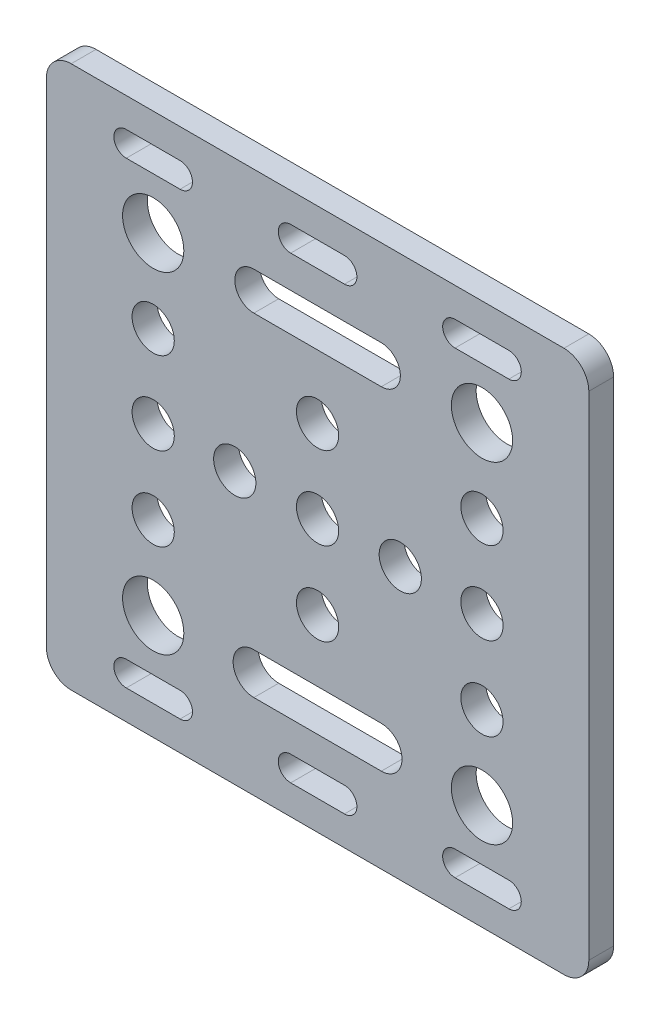
SolidWorks part; units mm, degrees
material "Plastique personnalisé"
ref_plane "Plan de face" through (0, 0, 0) normal (0, 0, 1) x (1, 0, 0)
ref_plane "Plan de dessus" through (0, 0, 0) normal (0, 1, 0) x (1, 0, 0)
ref_plane "Plan de droite" through (0, 0, 0) normal (1, 0, 0) x (0, 0, -1)
sketch "Esquisse1" plane through (0, 0, 0) normal (0, 0, 1) x (1, 0, 0)
  line L0 (99.2544, 347.4461) -> (164.2544, 347.4461) construction
  line L1 (98.9767, 347.4271) -> (98.9767, 324.6796) construction
  line L2 (101.9767, 347.4271) -> (161.4767, 347.4271)
  line L3 (98.9767, 344.4271) -> (98.9767, 284.9271)
  line L4 (101.9767, 281.9271) -> (161.4767, 281.9271)
  line L5 (164.4767, 344.4271) -> (164.4767, 284.9271)
  line L6 (98.9767, 324.6796) -> (111.8771, 324.6796) construction
  line L7 (98.9767, 324.6796) -> (131.7244, 324.6796) construction
  line L8 (98.9767, 324.6796) -> (151.5736, 324.6796) construction
  line L9 (98.9767, 347.4271) -> (98.9767, 314.7158) construction
  line L10 (105.9977, 347.4271) -> (105.9977, 314.6771) construction
  line L11 (98.9767, 347.4271) -> (98.9767, 342.3769) construction
  line L12 (98.9767, 342.3769) -> (111.8767, 342.3769) construction
  line L13 (108.6305, 342.3769) -> (115.1229, 342.3769) construction
  line L16 (108.6305, 343.8769) -> (115.1229, 343.8769)
  line L19 (108.6305, 340.8769) -> (115.1229, 340.8769)
  line L22 (104.4548, 347.4271) -> (104.4548, 342.3771) construction
  line L23 (128.4805, 342.3769) -> (134.9729, 342.3769) construction
  line L24 (128.4805, 343.8769) -> (134.9729, 343.8769)
  line L25 (128.4805, 340.8769) -> (134.9729, 340.8769)
  line L26 (148.3305, 342.3769) -> (154.8229, 342.3769) construction
  line L27 (148.3305, 343.8769) -> (154.8229, 343.8769)
  line L28 (148.3305, 340.8769) -> (154.8229, 340.8769)
  line L29 (102.5132, 286.9814) -> (111.8767, 286.9814) construction
  line L32 (108.6305, 286.9814) -> (115.1229, 286.9814) construction
  line L35 (108.6305, 288.4814) -> (115.1229, 288.4814)
  line L38 (102.5132, 347.4271) -> (102.5132, 286.9814) construction
  line L39 (98.9767, 342.3769) -> (111.8767, 342.3769) construction
  line L40 (111.8767, 342.3769) -> (111.8767, 280.6318) construction
  line L41 (108.6305, 285.4814) -> (115.1229, 285.4814)
  line L42 (128.4805, 286.9814) -> (134.9729, 286.9814) construction
  line L43 (128.4805, 288.4814) -> (134.9729, 288.4814)
  line L44 (128.4805, 285.4814) -> (134.9729, 285.4814)
  line L45 (148.3305, 286.9814) -> (154.8229, 286.9814) construction
  line L46 (148.3305, 288.4814) -> (154.8229, 288.4814)
  line L47 (148.3305, 285.4814) -> (154.8229, 285.4814)
  line L48 (98.9767, 314.7158) -> (111.8767, 314.7158) construction
  line L49 (111.8767, 314.7158) -> (131.7244, 314.7158) construction
  line L50 (131.7244, 314.7158) -> (151.5736, 314.7158) construction
  line L51 (98.9767, 314.7158) -> (121.7271, 314.7158) construction
  line L52 (98.9767, 314.7158) -> (141.7113, 314.7158) construction
  line L53 (98.9767, 347.4271) -> (98.9767, 304.674) construction
  line L54 (98.9767, 304.674) -> (111.8767, 304.674) construction
  line L55 (111.8767, 304.674) -> (131.7244, 304.674) construction
  line L56 (131.7244, 304.674) -> (151.5736, 304.674) construction
  line L57 (101.2288, 347.4271) -> (101.2288, 334.6754) construction
  line L58 (101.2288, 334.6754) -> (111.8767, 334.6754) construction
  line L59 (111.8767, 334.6754) -> (151.5767, 334.6754) construction
  line L60 (124.0318, 334.6754) -> (139.4216, 334.6754) construction
  line L61 (124.0318, 336.9754) -> (139.4216, 336.9754)
  line L62 (124.0318, 332.3754) -> (139.4216, 332.3754)
  line L63 (119.0951, 347.4271) -> (119.0951, 294.6771) construction
  line L64 (119.0951, 294.6771) -> (111.8767, 294.6771) construction
  line L65 (111.8767, 294.6771) -> (151.5767, 294.6771) construction
  line L66 (131.7267, 334.6754) -> (131.7267, 292.5418) construction
  line L67 (124.0318, 294.6771) -> (139.4216, 294.6771) construction
  line L68 (124.0318, 297.1771) -> (139.4216, 297.1771)
  line L69 (124.0318, 292.1771) -> (139.4216, 292.1771)
  circle A0 centre (111.8771, 324.6796) radius 2.55
  circle A1 centre (131.7244, 324.6796) radius 2.55
  circle A2 centre (151.5736, 324.6796) radius 2.55
  arc A9 (108.6305, 343.8769) -> (108.6305, 340.8769) centre (108.6305, 342.3769) ccw
  arc A10 (115.1229, 340.8769) -> (115.1229, 343.8769) centre (115.1229, 342.3769) ccw
  arc A11 (128.4805, 343.8769) -> (128.4805, 340.8769) centre (128.4805, 342.3769) ccw
  arc A12 (134.9729, 340.8769) -> (134.9729, 343.8769) centre (134.9729, 342.3769) ccw
  arc A13 (148.3305, 343.8769) -> (148.3305, 340.8769) centre (148.3305, 342.3769) ccw
  arc A14 (154.8229, 340.8769) -> (154.8229, 343.8769) centre (154.8229, 342.3769) ccw
  arc A21 (108.6305, 288.4814) -> (108.6305, 285.4814) centre (108.6305, 286.9814) ccw
  arc A22 (115.1229, 285.4814) -> (115.1229, 288.4814) centre (115.1229, 286.9814) ccw
  arc A23 (128.4805, 288.4814) -> (128.4805, 285.4814) centre (128.4805, 286.9814) ccw
  arc A24 (134.9729, 285.4814) -> (134.9729, 288.4814) centre (134.9729, 286.9814) ccw
  arc A25 (148.3305, 288.4814) -> (148.3305, 285.4814) centre (148.3305, 286.9814) ccw
  arc A26 (154.8229, 285.4814) -> (154.8229, 288.4814) centre (154.8229, 286.9814) ccw
  circle A27 centre (111.8767, 314.7158) radius 2.55
  circle A28 centre (131.7244, 314.7158) radius 2.55
  circle A29 centre (151.5736, 314.7158) radius 2.55
  circle A30 centre (121.7271, 314.7158) radius 2.55
  circle A31 centre (141.7113, 314.7158) radius 2.55
  circle A32 centre (111.8767, 304.674) radius 2.55
  circle A33 centre (131.7244, 304.674) radius 2.55
  circle A34 centre (151.5736, 304.674) radius 2.55
  circle A35 centre (111.8767, 334.6754) radius 3.7
  circle A36 centre (151.5767, 334.6754) radius 3.7
  arc A37 (124.0318, 336.9754) -> (124.0318, 332.3754) centre (124.0318, 334.6754) ccw
  arc A38 (139.4216, 332.3754) -> (139.4216, 336.9754) centre (139.4216, 334.6754) ccw
  circle A39 centre (111.8767, 294.6771) radius 3.7
  circle A40 centre (151.5767, 294.6771) radius 3.7
  arc A41 (124.0318, 297.1771) -> (124.0318, 292.1771) centre (124.0318, 294.6771) ccw
  arc A42 (139.4216, 292.1771) -> (139.4216, 297.1771) centre (139.4216, 294.6771) ccw
  arc A43 (161.4767, 347.4271) -> (164.4767, 344.4271) centre (161.4767, 344.4271) cw
  arc A44 (161.4767, 281.9271) -> (164.4767, 284.9271) centre (161.4767, 284.9271) ccw
  arc A45 (98.9767, 284.9271) -> (101.9767, 281.9271) centre (101.9767, 284.9271) ccw
  arc A46 (101.9767, 347.4271) -> (98.9767, 344.4271) centre (101.9767, 344.4271) ccw
  point P19 (111.8767, 342.3769)
  point P29 (131.7267, 342.3769)
  point P36 (151.5767, 342.3769)
  point P44 (111.8767, 286.9814)
  point P53 (131.7267, 286.9814)
  point P55 (131.7267, 288.5547)
  point P61 (151.5767, 286.9814)
  point P93 (131.7267, 334.6754)
  point P108 (131.7267, 294.6771)
  point P115 (164.4767, 347.4271)
  point P118 (164.4767, 281.9271)
  dimension "D4" = 12.9
  dimension "D6" = 3
  dimension "D7" = 3
  dimension "D9" = 52.75
  dimension "D10" = 3
  dimension "D1" = 65
  dimension "D2" = 65.5
  dimension "D3" = 65.5
  dimension "D5" = 5.05
  dimension "D8" = 32.75
extrude "Boss.-Extru.1" add sketch "Esquisse1" along normal blind 3
sketch "Esquisse2" plane through (0, 0, 3) normal (0, 0, 1) x (1, 0, 0)
  line L0 (131.7267, 347.4271) -> (131.7267, 281.9271) construction
  line L1 (161.4767, 347.4271) -> (101.9767, 347.4271) construction
  line L2 (101.9767, 281.9271) -> (161.4767, 281.9271) construction
ref_axis "Axe1" through (131.7267, 350.7478, 3) along (0, -1, 0)
sketch "Esquisse3" plane through (0, 0, 0) normal (0, 0, -1) x (-1, 0, 0)
  line L0 (-131.7267, 347.4271) -> (-131.7267, 268.7366) construction
  line L1 (-131.7267, 350.7478) -> (-131.7267, 279.0748) construction
ref_axis "axeinterne" through (131.7267, 347.4271, 0) along (0, -1, 0)
